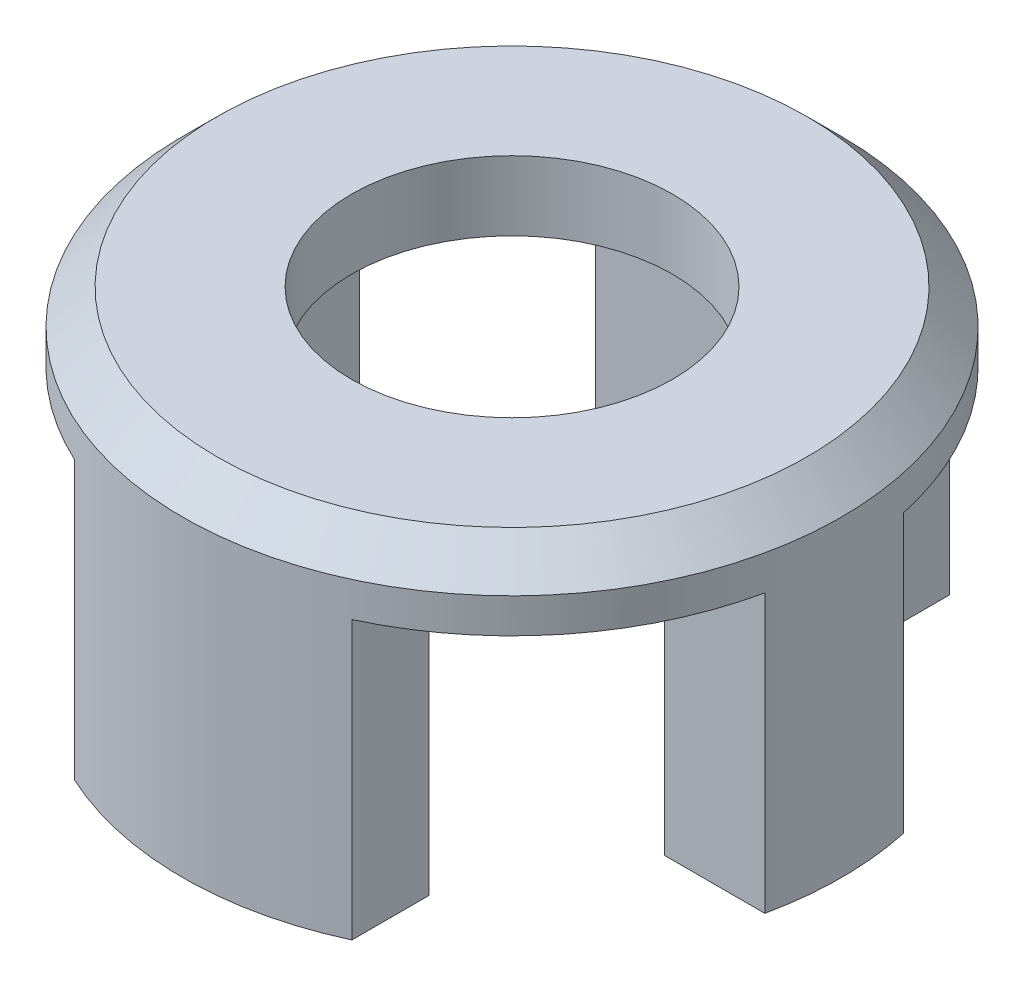
SolidWorks part; units mm, degrees
ref_plane "Front Plane" through (0, 0, 0) normal (0, 0, 1) x (1, 0, 0)
ref_plane "Top Plane" through (0, 0, 0) normal (0, 1, 0) x (1, 0, 0)
ref_plane "Right Plane" through (0, 0, 0) normal (1, 0, 0) x (0, 0, -1)
sketch "Sketch1" plane through (0, 0, 0) normal (0, 1, 0) x (1, 0, 0)
  line L0 (3.2, -1) -> (3.2, 1)
  line L1 (3.2, 1) -> (4.6435, 1)
  line L2 (3.2, -1) -> (4.6435, -1)
  line L3 (-5.812, 0) -> (7.7804, 0) construction
  line L4 (-4.6435, -1) -> (-3.2, -1)
  line L5 (-3.2, -1) -> (-3.2, 1)
  line L6 (-3.2, 1) -> (-4.6435, 1)
  line L7 (0, -6.4598) -> (0, 6.5341) construction
  line L8 (-2, -4.3084) -> (-2, -3.2)
  line L9 (-2, -3.2) -> (2, -3.2)
  line L10 (2, -3.2) -> (2, -4.3084)
  line L11 (-2, 4.3084) -> (-2, 3.2)
  line L12 (-2, 3.2) -> (2, 3.2)
  line L13 (2, 3.2) -> (2, 4.3084)
  circle A0 centre (0, 0) radius 4.75 construction
  arc A1 (-2, 4.3084) -> (2, 4.3084) centre (0, 0) cw
  arc A2 (4.6435, 1) -> (4.6435, -1) centre (0, 0) cw
  arc A3 (2, -4.3084) -> (-2, -4.3084) centre (0, 0) cw
  arc A4 (-4.6435, -1) -> (-4.6435, 1) centre (0, 0) cw
  dimension "D1" = 9.5
  dimension "D2" = 2
  dimension "D3" = 3.2
  dimension "D4" = 4
  dimension "D5" = 3.2
ref_axis "Axis1" through (0, -16.0781, 0) along (0, 1, 0)
extrude "Boss-Extrude1" add sketch "Sketch1" along normal blind 5
sketch "Sketch2" plane through (0, 5, 0) normal (0, 1, 0) x (1, 0, 0)
  circle A0 centre (0, 0) radius 4.75
  circle A1 centre (0, 0) radius 2.3134
extrude "Boss-Extrude2" add sketch "Sketch2" against normal blind 1
chamfer "Chamfer1" distance 0.5 angle 45 1 edges at (0, 5, -4.75)
